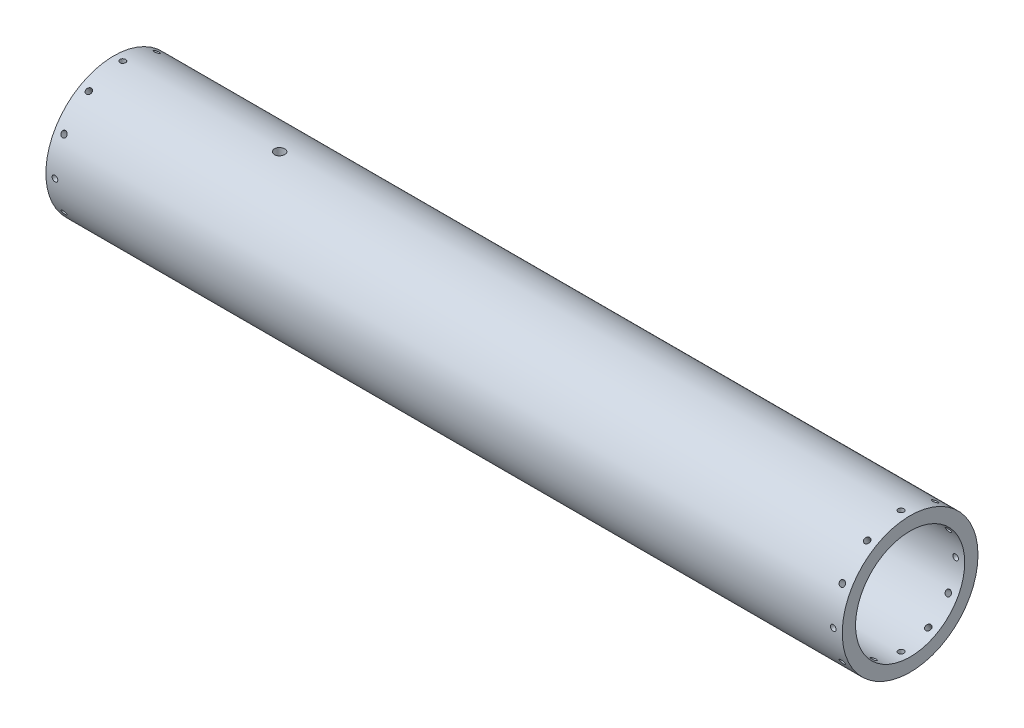
SolidWorks part; units mm, degrees
material "7075-T6 (SN)"
ref_plane "Front Plane" through (0, 0, 0) normal (0, 0, 1) x (1, 0, 0)
ref_plane "Top Plane" through (0, 0, 0) normal (0, 1, 0) x (1, 0, 0)
ref_plane "Right Plane" through (0, 0, 0) normal (1, 0, 0) x (0, 0, -1)
sketch "Sketch1" plane through (0, 0, 0) normal (1, 0, 0) x (0, 0, -1)
  circle A0 centre (0, 0) radius 45.9486
  circle A1 centre (0, 0) radius 57.15
  dimension "D1" = 91.8972
  dimension "D2" = 114.3
extrude "Boss-Extrude1" add sketch "Sketch1" along normal blind 670.56
sketch "Sketch4" plane through (0, 0, 0) normal (0, 0, 1) x (1, 0, 0)
  line L0 (0, 0) -> (0, 88.0135) construction
  line L1 (0, 57.15) -> (0, -57.15) construction
  line L2 (0, -55) -> (0, 55) construction
  line L3 (0, 0) -> (-48.5735, 0) construction
ref_plane "Plane1" through (0, 57.15, 0) normal (0, 1, 0) x (1, 0, 0)
sketch "Sketch6" plane through (0, 57.15, 0) normal (0, 1, 0) x (1, 0, 0)
  line L0 (0, 57.15) -> (0, -57.15) construction
  circle A0 centre (7.62, 0) radius 2.413
  point P4 (0, 0)
  dimension "D1" = 4.826
  dimension "D2" = 7.62
extrude "Cut-Extrude1" cut sketch "Sketch6" against normal blind 15.24
sketch "Sketch7" plane through (0, 57.15, 0) normal (0, 1, 0) x (1, 0, 0)
  line L0 (670.56, -57.15) -> (670.56, 57.15) construction
  circle A0 centre (662.94, 0) radius 2.413
  point P4 (0, 0)
  point P8 (670.56, 0)
  dimension "D2" = 4.826
  dimension "D1" = 7.62
extrude "Cut-Extrude2" cut sketch "Sketch7" against normal blind 15.24
pattern_circular "CirPattern2" count 12 over 360 about axis through (670.56, 0, 0) along (1, 0, 0) of "Cut-Extrude2"
pattern_circular "CirPattern3" count 12 over 360 about axis through (0, 0, 0) along (-1, 0, 0) of "Cut-Extrude1" reverse direction yes
sketch "Sketch8" plane through (0, 57.15, 0) normal (0, 1, 0) x (1, 0, 0)
  line L0 (0, 57.15) -> (0, -57.15) construction
  circle A0 centre (139.7, 0) radius 4.3053
  point P4 (139.7, 0)
  dimension "D2" = 8.6106
  dimension "D1" = 139.7
extrude "Cut-Extrude3" cut sketch "Sketch8" against normal through all
